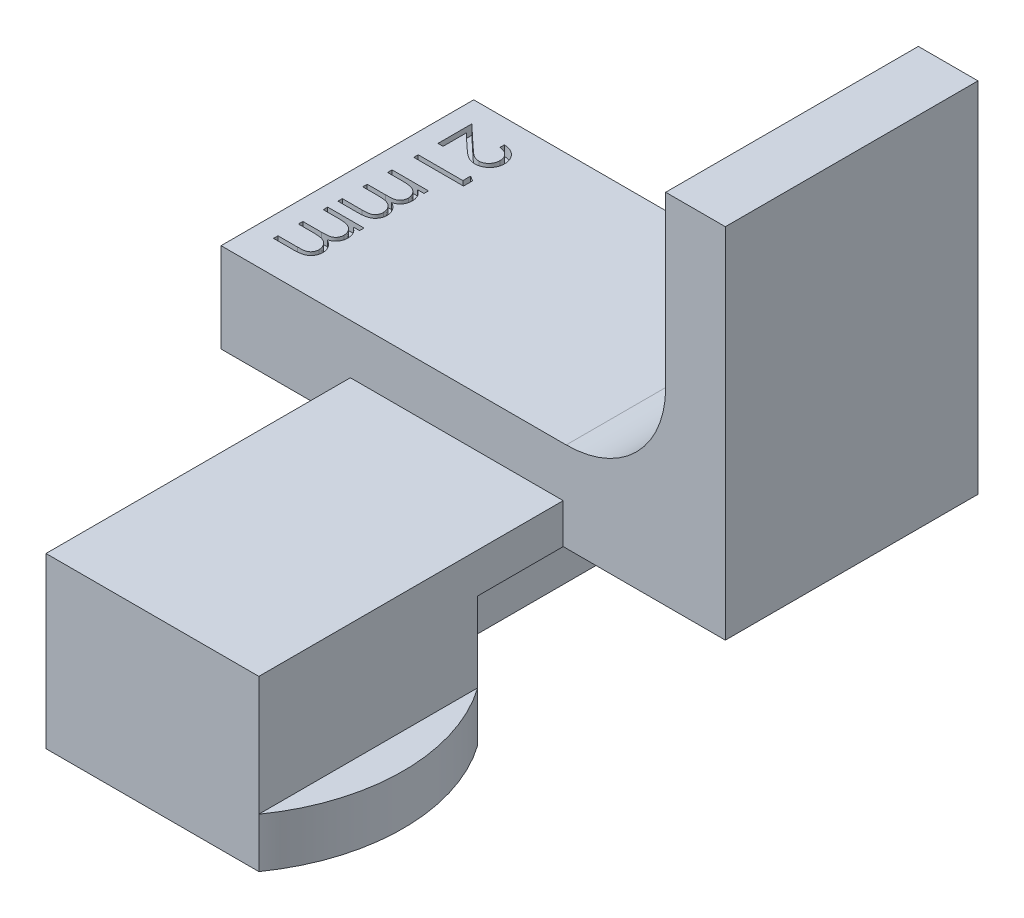
SolidWorks part; units mm, degrees
ref_plane "Front Plane" through (0, 0, 0) normal (0, 0, 1) x (1, 0, 0)
ref_plane "Top Plane" through (0, 0, 0) normal (0, 1, 0) x (1, 0, 0)
ref_plane "Right Plane" through (0, 0, 0) normal (1, 0, 0) x (0, 0, -1)
sketch "Sketch1" plane through (0, 0, 0) normal (0, 0, 1) x (1, 0, 0)
  line L0 (0, 0) -> (0, -4)
  line L1 (0, -4) -> (-1.75, -4)
  line L2 (-1.75, -4) -> (-1.75, -6.5)
  line L8 (12.45, -6.5) -> (12.45, -4)
  line L9 (12.45, -4) -> (10.7, -4)
  line L10 (10.7, -4) -> (10.7, 0)
  line L11 (10.7, 0) -> (18.85, 0)
  line L12 (18.85, 0) -> (18.85, 18)
  line L13 (18.85, 18) -> (15.85, 18)
  line L14 (15.85, 18) -> (15.85, 4.5)
  line L15 (15.85, 4.5) -> (-6.5, 4.5)
  line L16 (-6.5, 4.5) -> (-6.5, 0)
  line L17 (-6.5, 0) -> (0, 0)
  line L18 (5.35, -6.5) -> (5.35, 15) construction
  line L19 (-1.75, -6.5) -> (12.45, -6.5)
  circle A0 centre (5.35, 15) radius 10.5 construction
  point P3 (5.35, -6.5)
  dimension "D9" = 15
  dimension "D8" = 21
  dimension "D2" = 2.5
  dimension "D3" = 10.7
  dimension "D4" = 4
  dimension "D5" = 14.2
  dimension "D6" = 3
  dimension "D7" = 3
  dimension "D10" = 6.5
extrude "Boss-Extrude1" add sketch "Sketch1" along normal blind 12.7
fillet "Fillet1" radius 5 1 edges at (15.85, 4.5, 6.35)
sketch "Sketch3" plane through (0, 0, 12.7) normal (0, 0, 1) x (1, 0, 0)
  line L0 (0, 0) -> (0, 2)
  line L1 (0, 2) -> (10.7, 2)
  line L2 (10.7, 2) -> (10.7, 0)
  line L14 (-6.5, 0) -> (0, 0)
  line L15 (0, 0) -> (0, -4)
  line L16 (0, -4) -> (-1.75, -4)
  line L17 (-1.75, -4) -> (-1.75, -6.5)
  line L18 (-1.75, -6.5) -> (12.45, -6.5)
  line L19 (12.45, -6.5) -> (12.45, -4)
  line L20 (12.45, -4) -> (10.7, -4)
  line L21 (10.7, -4) -> (10.7, 0)
  line L22 (10.7, 0) -> (18.85, 0)
  line L23 (18.85, 0) -> (18.85, 18)
  line L24 (18.85, 18) -> (15.85, 18)
  line L25 (15.85, 18) -> (15.85, 9.5)
  line L26 (10.85, 4.5) -> (-6.5, 4.5)
  line L27 (-6.5, 4.5) -> (-6.5, 0)
  line L29 (0, 0) -> (0, -4)
  line L30 (0, -4) -> (-1.75, -4)
  line L31 (-1.75, -4) -> (-1.75, -6.5)
  line L32 (-1.75, -6.5) -> (12.45, -6.5)
  line L33 (12.45, -6.5) -> (12.45, -4)
  line L34 (12.45, -4) -> (10.7, -4)
  line L35 (10.7, -4) -> (10.7, 0)
  arc A1 (10.85, 4.5) -> (15.85, 9.5) centre (10.85, 9.5) ccw
  dimension "D2" = 2
  dimension "D1" = 0
extrude "Boss-Extrude2" add sketch "Sketch3" along normal blind 28 from surface starting at face at (7.4057, 1.631, 0)
sketch "Sketch4" plane through (0, 0, 0) normal (0, 0, -1) x (-1, 0, 0)
  line L0 (6.5, 0) -> (0, 0) construction
  line L1 (-12.45, -6.5) -> (1.75, -6.5)
  line L2 (-12.45, -6.5) -> (-12.45, -2)
  line L3 (-12.45, -2) -> (1.75, -2)
  line L4 (1.75, -6.5) -> (1.75, -2)
  dimension "D1" = 2
extrude "Cut-Extrude2" cut sketch "Sketch4" against normal blind 17
sketch "Sketch2" plane through (0, -4, 0) normal (0, 1, 0) x (1, 0, 0)
  line L0 (0, -28) -> (10.7, -28)
  line L1 (10.7, -17) -> (0, -17)
  line L6 (12.45, -28) -> (12.45, -17) construction
  line L7 (-1.75, -28) -> (-1.75, -17) construction
  arc A4 (0, -17) -> (0, -28) centre (7.7679, -22.5) ccw
  arc A6 (10.7, -28) -> (10.7, -17) centre (2.9321, -22.5) ccw
extrude "Cut-Extrude1" cut sketch "Sketch2" against normal blind 10 flip side to cut
sketch "Sketch5" plane through (0, 4.5, 0) normal (0, 1, 0) x (1, 0, 0)
  line L0 (-5.5, -1) -> (-5.5, -10.9086) construction
  line L1 (-6.5, -12.7) -> (-6.5, 0) construction
  line L2 (10.85, 0) -> (-6.5, 0) construction
  text T0 "21mm" font "Century Gothic" height 2.5
  dimension "D1" = 1
  dimension "D2" = 1
extrude "Cut-Extrude3" cut sketch "Sketch5" against normal blind 0.5
sketch "Sketch6" plane through (0, 0, 0) normal (-1, 0, 0) x (0, 0, 1)
  line L1 (0, -2) -> (17, -2)
  line L2 (0, -2) -> (0, 0)
  line L3 (0, 0) -> (17, 0)
  line L4 (17, -2) -> (17, 0)
  point P4 (0, 0)
  point P5 (17, -2)
extrude "Cut-Extrude4" cut sketch "Sketch6" against normal blind 0.35
extrude "Cut-Extrude5" cut sketch "Sketch6<2>" along normal blind 0.35 from surface starting at face at (10.7, -1, 14.425)
sketch "Sketch6<2>" plane through (0, 0, 0) normal (-1, 0, 0) x (0, 0, 1) same geometry as "Sketch6"
